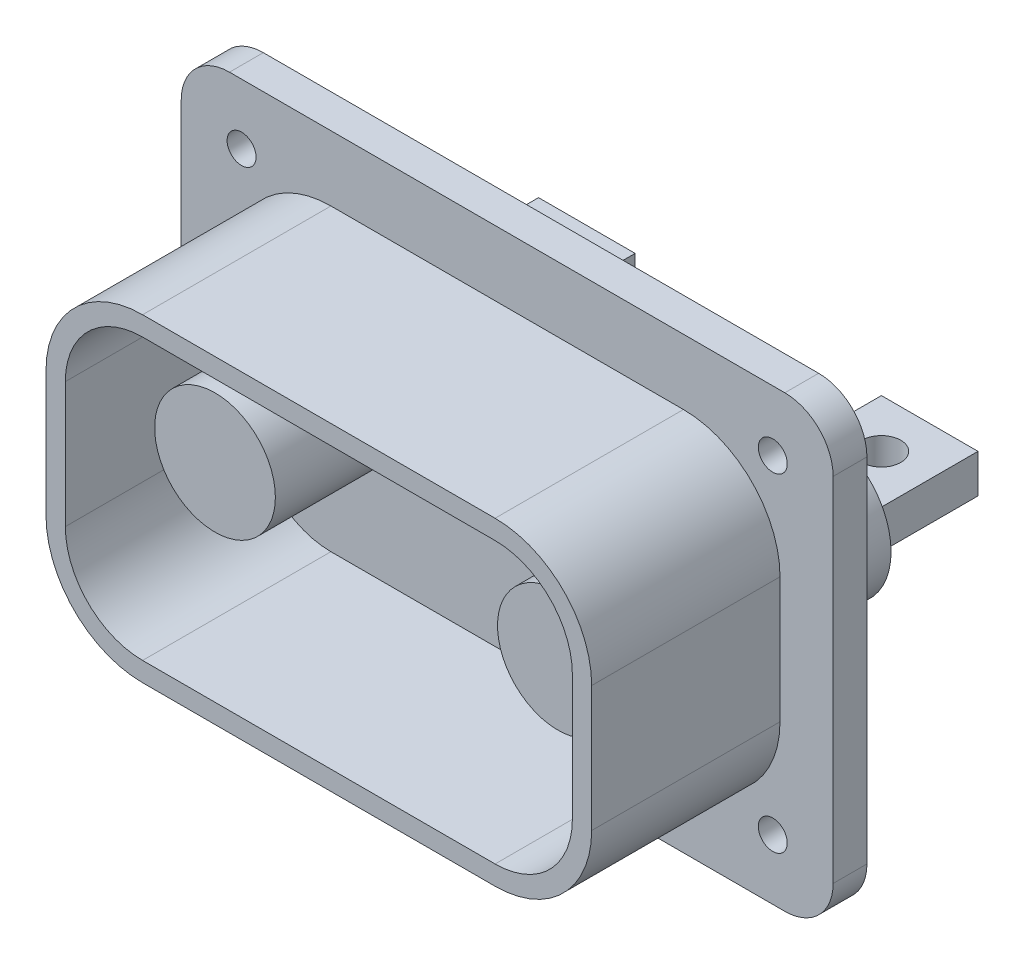
SolidWorks part; units mm, degrees
ref_plane "X-Y Datum" through (0, 0, 0) normal (0, 0, 1) x (1, 0, 0)
ref_plane "X-Z Datum" through (0, 0, 0) normal (0, 1, 0) x (1, 0, 0)
ref_plane "Y-Z Datum" through (0, 0, 0) normal (1, 0, 0) x (0, 0, -1)
sketch "Sketch1" plane through (0, 0, 0) normal (0, 0, 1) x (1, 0, 0)
  line L1 (-67.5, -46.5) -> (67.5, -46.5)
  line L2 (-67.5, -46.5) -> (-67.5, 46.5)
  line L3 (-67.5, 46.5) -> (67.5, 46.5)
  line L4 (67.5, -46.5) -> (67.5, 46.5)
  line L5 (-67.5, -46.5) -> (67.5, 46.5) construction
  line L6 (-67.5, 46.5) -> (67.5, -46.5) construction
  line L11 (-50.4972, -34.787) -> (50.4972, 34.787) construction
  line L12 (-50.4972, 34.787) -> (50.4972, -34.787) construction
  line L13 (-55, 34) -> (55, 34) construction
  line L14 (-55, 34) -> (-55, -34) construction
  line L15 (-55, -34) -> (55, -34) construction
  line L16 (55, 34) -> (55, -34) construction
  line L17 (-55, 34) -> (55, -34) construction
  line L18 (-55, -34) -> (55, 34) construction
  circle A4 centre (-55, 34) radius 3
  circle A5 centre (55, 34) radius 3
  circle A6 centre (55, -34) radius 3
  circle A7 centre (-55, -34) radius 3
  point P0 (0, 0)
  point P6 (0, 0)
  point P12 (0, 0)
  dimension "D3" = 110
  dimension "D4" = 68
  dimension "D5" = 6
  dimension "D1" = 135
  dimension "D2" = 93
extrude "Boss-Extrude1" add sketch "Sketch1" along normal blind 7 contours L1 L4 L3 L2 A4 | A4 region at (0, 0, 0)
sketch "Sketch2" plane through (0, 0, 7) normal (0, 0, 1) x (1, 0, 0)
  line L0 (-35.5, 0) -> (35.5, 0) construction
  line L5 (-52.5, 13) -> (-52.5, -13)
  line L6 (-36.5, 33) -> (36.5, 33)
  line L7 (-56.5, 13) -> (-56.5, -13)
  line L8 (-36.5, -33) -> (36.5, -33)
  line L9 (56.5, 13) -> (56.5, -13)
  line L10 (-56.5, 33) -> (56.5, -33) construction
  line L11 (-56.5, -33) -> (56.5, 33) construction
  line L12 (-36.5, -29) -> (36.5, -29)
  line L13 (52.5, 13) -> (52.5, -13)
  line L14 (-36.5, 29) -> (36.5, 29)
  circle A4 centre (-35.5, 0) radius 4 construction
  circle A5 centre (35.5, 0) radius 4 construction
  arc A6 (36.5, -33) -> (56.5, -13) centre (36.5, -13) ccw
  arc A7 (36.5, 33) -> (56.5, 13) centre (36.5, 13) cw
  arc A8 (-36.5, 33) -> (-56.5, 13) centre (-36.5, 13) ccw
  arc A9 (-56.5, -13) -> (-36.5, -33) centre (-36.5, -13) ccw
  arc A10 (-52.5, -13) -> (-36.5, -29) centre (-36.5, -13) ccw
  arc A11 (36.5, -29) -> (52.5, -13) centre (36.5, -13) ccw
  arc A12 (36.5, 29) -> (52.5, 13) centre (36.5, 13) cw
  arc A13 (-36.5, 29) -> (-52.5, 13) centre (-36.5, 13) ccw
  point P2 (0, 0)
  point P4 (0, 0)
  dimension "D1" = 8
  dimension "D5" = 20
  dimension "D2" = 71
  dimension "D3" = 113
  dimension "D4" = 66
  dimension "D6" = 4
extrude "Boss-Extrude2" add sketch "Sketch2" along normal blind 39
fillet "Fillet1" radius 10 4 edges at (67.5, 46.5, 3.5) (67.5, -46.5, 3.5) (-67.5, -46.5, 3.5) (-67.5, 46.5, 3.5)
sketch "Sketch3" plane through (0, 0, 0) normal (0, 0, -1) x (-1, 0, 0)
  line L0 (-35.5, 0) -> (35.5, 0) construction
  circle A0 centre (-35.5, 0) radius 15
  circle A1 centre (35.5, 0) radius 15
  point P11 (0, 0)
  dimension "D1" = 71
  dimension "D2" = 30
extrude "Boss-Extrude3" add sketch "Sketch3" along normal blind 22 contours A0 | A1 region at (35.5, 0, 0) region at (-35.5, 0, 0)
sketch "Sketch5" plane through (0, 0, -22) normal (0, 0, -1) x (-1, 0, 0)
  line L1 (-45.5, 4) -> (-25.5, 4)
  line L2 (-45.5, 4) -> (-45.5, -4)
  line L3 (-45.5, -4) -> (-25.5, -4)
  line L4 (-25.5, 4) -> (-25.5, -4)
  line L5 (-45.5, 4) -> (-25.5, -4) construction
  line L6 (-45.5, -4) -> (-25.5, 4) construction
  line L7 (25.5, 4) -> (45.5, 4)
  line L8 (25.5, 4) -> (25.5, -4)
  line L9 (25.5, -4) -> (45.5, -4)
  line L10 (45.5, 4) -> (45.5, -4)
  line L11 (25.5, 4) -> (45.5, -4) construction
  line L12 (25.5, -4) -> (45.5, 4) construction
  point P0 (-35.5, 0)
  point P6 (35.5, 0)
  dimension "D1" = 8
  dimension "D2" = 20
extrude "Boss-Extrude4" add sketch "Sketch5" along normal blind 23
sketch "Sketch6" plane through (0, 4, 0) normal (0, 1, 0) x (1, 0, 0)
  line L0 (35.5, 45) -> (35.5, 22) construction
  line L1 (25.5, 45) -> (45.5, 45) construction
  line L2 (50.5, 22) -> (20.5, 22) construction
  line L3 (0, -43.0151) -> (0, 43.0151) construction
  circle A0 centre (35.5, 35) radius 4
  circle A1 centre (-35.5, 35) radius 4
  dimension "D1" = 8
  dimension "D2" = 10
extrude "Cut-Extrude1" cut sketch "Sketch6" against normal through all
sketch "Sketch7" plane through (0, 0, 7) normal (0, 0, 1) x (1, 0, 0)
  line L0 (-35.5, 0) -> (35.5, 0) construction
  circle A0 centre (-35.5, 0) radius 12.5
  circle A1 centre (35.5, 0) radius 12.5
  point P4 (0, 0)
  dimension "D2" = 25
  dimension "D1" = 71
extrude "Boss-Extrude5" add sketch "Sketch7" along normal blind 25
